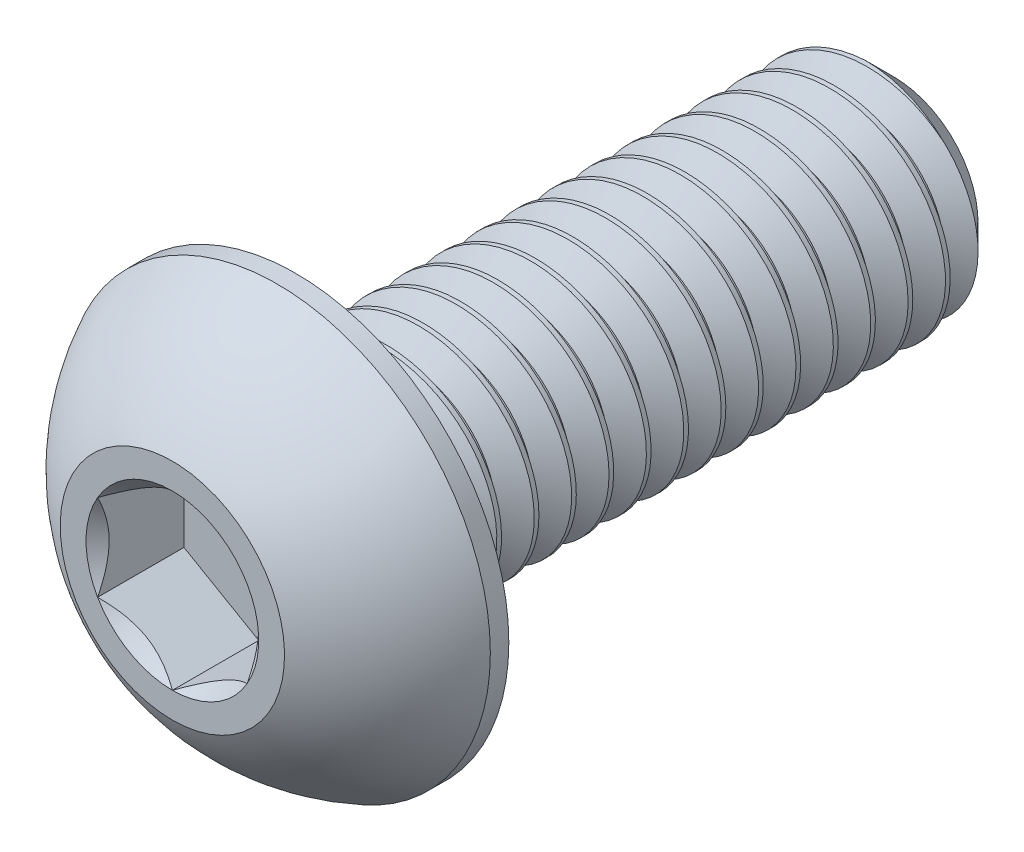
SolidWorks part; units mm, degrees
note: '?' marks a value the reader was unsure of.
material "Alloy Steel (SS)"
ref_plane "Front" through (0, 0, 0) normal (0, 0, 1) x (1, 0, 0)
ref_plane "Top" through (0, 0, 0) normal (0, 1, 0) x (1, 0, 0)
ref_plane "Right" through (0, 0, 0) normal (1, 0, 0) x (0, 0, -1)
sketch "Sketch1" plane through (0, 0, 0) normal (1, 0, 0) x (0, 0, -1)
  line L2 (1.65, 1.5) -> (9.65, 1.5)
  line L3 (9.65, 1.5) -> (9.65, 0)
  line L4 (9.65, 0) -> (1.65, 0)
  line L6 (1.4025, 2.85) -> (1.65, 2.85) construction
  line L7 (9.65, 1.5) -> (9.65, -1.5) construction
  line L8 (0, 0) -> (1.65, 0) construction
  line L9 (1.65, 2.85) -> (1.65, -2.85) construction
  line L11 (1.65, 1.5) -> (1.65, 0)
  line L13 (0, 1) -> (0, -1) construction
  line L14 (0, 1) -> (0, 1.5) construction
  arc A3 (0, 1.5) -> (1.4025, 2.85) centre (2.7948, 0) cw construction
  dimension "D1" = 0.2475
revolve "Revolve1" add sketch "Sketch1" angle 360 mid plane about L4
sketch "Sketch3" plane through (0, 0, -9.65) normal (0, 0, -1) x (-1, 0, 0)
  circle A0 centre (0, 0) radius 1.5
curve "Helix/Spiral1" pitch 0.5 height 8.5 turns 17
chamfer "Chamfer1" distance 0.375 angle 45 1 edges at (0, 1.5, -9.65)
sketch "Sketch7" plane through (0, 0, 0) normal (1, 0, 0) x (0, 0, -1)
  line L6 (1.4025, 2.85) -> (1.65, 2.85) construction
  line L8 (0, 0) -> (1.65, 0) construction
  line L11 (1.65, 2.85) -> (1.65, -2.85) construction
  line L12 (1.4025, 2.85) -> (1.65, 2.85)
  line L13 (0, 0) -> (1.65, 0)
  line L14 (0, 1) -> (0, -1) construction
  line L15 (1.65, 2.85) -> (1.65, 0)
  line L16 (0, 1.5) -> (0, 0)
  arc A2 (1.4025, 2.85) -> (0, 1.5) centre (2.7948, 0) ccw construction
  arc A3 (1.4025, 2.85) -> (0, 1.5) centre (2.7948, 0) ccw
revolve "Revolve2" add sketch "Sketch7" angle 360 mid plane about L13
sketch "Sketch5" plane through (0, 0, 0) normal (0, 0, 1) x (1, 0, 0)
  line L1 (1, -0.5774) -> (1, 0.5774)
  line L2 (1, 0.5774) -> (0, 1.1547)
  line L3 (0, 1.1547) -> (-1, 0.5774)
  line L4 (-1, 0.5774) -> (-1, -0.5774)
  line L5 (-1, -0.5774) -> (0, -1.1547)
  line L6 (0, -1.1547) -> (1, -0.5774)
  circle A0 centre (0, 0) radius 1 construction
extrude "Cut-Extrude2" cut sketch "Sketch5" against normal blind 1.155
sketch "Sketch6" plane through (0, 0, 0) normal (0, 0, 1) x (1, 0, 0)
  circle A0 centre (0, 0) radius 1.1547
extrude "Cut-Extrude3" cut sketch "Sketch6" against normal blind 1.155 draft 45
sketch "Sketch2" plane through (0, 0, 0) normal (1, 0, 0) x (0, 0, -1)
  line L0 (9.275, 1.5) -> (9.7125, 1.5)
  line L1 (9.7125, 1.5) -> (9.525, 1.1752)
  line L2 (9.525, 1.1752) -> (9.4625, 1.1752)
  line L3 (9.4625, 1.1752) -> (9.275, 1.5)
  line L4 (9.3687, 1.3376) -> (9.6187, 1.3376) construction
  dimension "D1" = 60
  dimension "D2" = 0.0625
  dimension "D3" = 0.25
sweep "Cut-Sweep1" cut profiles "Sketch2" path "Helix/Spiral1"
sketch "Sketch10" plane through (0, 0, 0) normal (1, 0, 0) x (0, 0, -1)
  line L0 (9.65, 1.5) -> (9.65, -1.5) construction
  point P0 (8.9, -1.5)
  dimension "D1" = 0.75
ref_axis "Center Axis 1" through (0, 0, -8.1113) along (0, 0, 1)?
ref_plane "Contact Plane 1" through (0, 0, -1.65) normal (0, 0, -1) x (-1, 0, 0)
ref_plane "Contact Plane 2" through (0, 0, 0) normal (0, 0, 1) x (1, 0, 0)
equation "\"D3@Helix/Spiral1\" = \"Lg@Sketch1\" + \"D4@Helix/Spiral1\""
equation "\"D2@Sketch2\" = \"D4@Helix/Spiral1\" * .125"
equation "\"D3@Sketch2\" = \"D4@Helix/Spiral1\" * .5"
equation "\"D1@Chamfer1\" = \"D4@Helix/Spiral1\" * .75"
equation "\"D1@Cut-Extrude2\" = \"Head Ht@Sketch1\" * .7"
equation "\"D1@Sketch1\" = \"Head Ht@Sketch1\" * .15"
equation "\"D1@Sketch10\" = \"D4@Helix/Spiral1\" * 1.5"
equation "\"D1@Cut-Extrude3\" = \"D1@Cut-Extrude2\""
